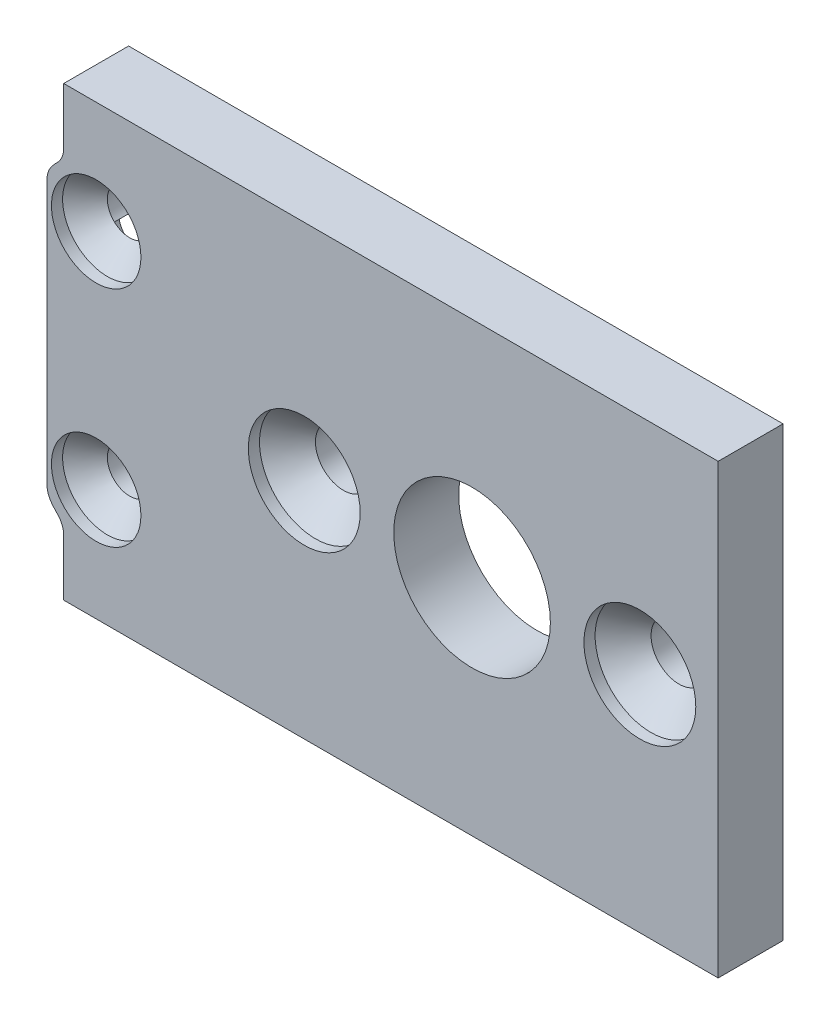
SolidWorks part; units mm, degrees
ref_plane "Front Plane" through (0, 0, 0) normal (0, 0, 1) x (1, 0, 0)
ref_plane "Top Plane" through (0, 0, 0) normal (0, 1, 0) x (1, 0, 0)
ref_plane "Right Plane" through (0, 0, 0) normal (1, 0, 0) x (0, 0, -1)
sketch "Sketch1" plane through (0, 0, 0) normal (0, 0, 1) x (1, 0, 0)
  line L1 (-92.5, 10) -> (92.5, 10)
  line L2 (-92.5, 10) -> (-92.5, -10)
  line L3 (-92.5, -10) -> (92.5, -10)
  line L4 (92.5, 10) -> (92.5, -10)
  line L5 (-92.5, 10) -> (92.5, -10) construction
  line L6 (-92.5, -10) -> (92.5, 10) construction
  point P0 (0, 0)
  dimension "D1" = 20
  dimension "D2" = 185
extrude "Base shape" add sketch "Sketch1" against normal blind 2.9
sketch "Sketch2" plane through (0, 0, 0) normal (0, 0, 1) x (1, 0, 0)
  line L0 (-83.5, 10) -> (-83.5, -10) construction
  line L1 (92.5, 10) -> (-92.5, 10) construction
  line L2 (-92.5, -10) -> (92.5, -10) construction
  line L3 (-92.5, 10) -> (-92.5, -10) construction
  line L4 (-92.5, 0) -> (92.5, 0) construction
  line L5 (92.5, -10) -> (92.5, 10) construction
  line L6 (-73.5, 10) -> (-73.5, -10) construction
  line L7 (0, 10) -> (0, -10) construction
  line L8 (73.5, 5) -> (92.5, 5) construction
  line L9 (-73.5, 3.5) -> (-92.5, 3.5) construction
  line L11 (80.5, -7) -> (66.5, -7)
  line L12 (80.5, -7) -> (80.5, 7)
  line L13 (80.5, 7) -> (66.5, 7)
  line L14 (66.5, -7) -> (66.5, 7)
  line L15 (80.5, -7) -> (66.5, 7) construction
  line L16 (80.5, 7) -> (66.5, -7) construction
  circle A0 centre (-73.5, 0) radius 10
  circle A1 centre (-81, 0) radius 1.25
  circle A2 centre (-66, 0) radius 1.25
  circle A3 centre (-73.5, 0) radius 3.5
  circle A4 centre (73.5, 0) radius 5
  circle A5 centre (66.5, 7) radius 1.25
  circle A6 centre (80.5, 7) radius 1.25
  circle A7 centre (80.5, -7) radius 1.25
  circle A8 centre (66.5, -7) radius 1.25
  dimension "D2" = 20
  dimension "D3" = 2.5
  dimension "D4" = 15
  dimension "D5" = 7
  dimension "D6" = 10
  dimension "D8" = 2.5
  dimension "D1" = 147
  dimension "D7" = 14
extrude "Motor cutouts" cut sketch "Sketch2" against normal up to next contours A5 | A6 | A7 | A8 | A1 | A2 | A3 | A4
hole_wizard "Motor M2.5 countersunks" positions "Sketch3" profile "Sketch4" countersink size "M2.5" standard "ANSI Metric" end condition through all
sketch "Sketch3" plane through (0, 0, 0) normal (0, 0, 1) x (1, 0, 0)
  point P0 (-81, 0)
  point P3 (-66, 0)
  point P7 (66.5, 7)
  point P10 (80.5, 7)
  point P13 (66.5, -7)
  point P16 (80.5, -7)
sketch "Sketch4" plane through (-81, 0, 0) normal (1, 0, 0) x (0, -1, 0)
  line L0 (0, 0) -> (0, 2.9)
  line L1 (0, 2.9) -> (1.25, 2.9)
  line L2 (1.25, 2.9) -> (1.25, 1.75)
  line L3 (1.25, 1.75) -> (2.5, 0.5)
  line L4 (2.5, 0.5) -> (2.5, 0)
  line L6 (2.5, 0) -> (0, 0)
  line L7 (-1.25, 1.75) -> (-2.5, 0.5) construction
  line L11 (0, -6.35) -> (0, 107.95) construction
  dimension "Thru Hole Dia." = 2.5
  dimension "Thru Hole Depth" = 2.9
  dimension "C'Sink Dia." = 5
  dimension "C'Sink Angle" = 90
  dimension "Head Clearance" = 0.5
sketch "Sketch5" plane through (0, 0, -2.9) normal (0, 0, -1) x (-1, 0, 0)
  line L0 (0, 10) -> (0, -10) construction
  line L3 (-92.5, 10) -> (92.5, 10) construction
  line L4 (92.5, -10) -> (-92.5, -10) construction
  line L5 (-60, -7) -> (60, -7) construction
  line L6 (-60, -6) -> (60, -6)
  line L7 (-60, -8) -> (60, -8)
  arc A0 (-60, -6) -> (-60, -8) centre (-60, -7) ccw
  arc A1 (60, -8) -> (60, -6) centre (60, -7) ccw
  point P8 (0, -7)
  dimension "D1" = 120
  dimension "D2" = 2
  dimension "D3" = 2
extrude "PCB slot" cut sketch "Sketch5" against normal blind 0.775
sketch "Sketch6" plane through (0, 0, 0) normal (0, 0, 1) x (1, 0, 0)
  line L0 (90.3, 10) -> (90.3, -10) construction
  line L1 (92.5, 10) -> (-92.5, 10) construction
  line L2 (-92.5, -10) -> (92.5, -10) construction
  line L3 (92.5, -10) -> (92.5, 10) construction
  line L4 (92.5, 0) -> (-92.5, 0) construction
  line L5 (-92.5, 10) -> (-92.5, -10) construction
  line L6 (0, 10) -> (0, -10) construction
  circle A0 centre (90.3, 5) radius 1
  circle A2 centre (90.3, -5) radius 1
  circle A3 centre (-90.3, -5) radius 1
  circle A5 centre (-90.3, 5) radius 1
  dimension "D2" = 2
  dimension "D1" = 2.2
  dimension "D3" = 10
extrude "End plate holes" cut sketch "Sketch6" against normal up to next
hole_wizard "CSK for M2 Flat Head Machine Screw3" positions "Sketch10" profile "Sketch9" countersink size "M2" standard "ANSI Metric" end condition through all
sketch "Sketch10" plane through (0, 0, 0) normal (0, 0, 1) x (1, 0, 0)
  point P2 (90.3, 5)
  point P8 (90.3, -5)
  point P11 (-90.3, 5)
  point P17 (-90.3, -5)
sketch "Sketch9" plane through (90.3, 5, 0) normal (1, 0, 0) x (0, -1, 0)
  line L0 (0, 0) -> (0, 2.9)
  line L1 (0, 2.9) -> (1, 2.9)
  line L2 (1, 2.9) -> (1, 1.5)
  line L3 (1, 1.5) -> (2, 0.5)
  line L4 (2, 0.5) -> (2, 0)
  line L6 (2, 0) -> (0, 0)
  line L7 (-1, 1.5) -> (-2, 0.5) construction
  line L11 (0, -6.35) -> (0, 107.95) construction
  dimension "Thru Hole Dia." = 2
  dimension "Thru Hole Depth" = 2.9
  dimension "C'Sink Dia." = 4
  dimension "C'Sink Angle" = 90
  dimension "Head Clearance" = 0.5
sketch "Sketch12" plane through (0, 0, -2.9) normal (0, 0, -1) x (-1, 0, 0)
  line L0 (-92.5, 0) -> (92.5, 0) construction
  line L1 (-92.5, -10) -> (-92.5, 10) construction
  line L2 (92.5, 10) -> (92.5, -10) construction
  line L3 (-90.3, 5) -> (-90.3, -5) construction
  line L4 (-88.7, 4) -> (-91.9, 0.8) construction
  line L5 (-91.9, 4) -> (-88.7, 4)
  line L6 (-91.9, 4) -> (-91.9, -4)
  line L7 (-91.9, -4) -> (-88.7, -4)
  line L8 (-88.7, 4) -> (-88.7, -4)
  line L9 (-91.9, 4) -> (-88.7, -4) construction
  line L10 (-91.9, -4) -> (-88.7, 4) construction
  line L11 (0, 10) -> (0, -10) construction
  line L12 (-92.5, 10) -> (92.5, 10) construction
  line L13 (92.5, -10) -> (-92.5, -10) construction
  line L14 (91.9, -4) -> (88.7, -4)
  line L15 (91.9, 4) -> (88.7, 4)
  line L16 (91.9, 4) -> (91.9, -4)
  line L17 (88.7, 4) -> (88.7, -4)
  circle A0 centre (-89.4071, 3.2929) radius 1
  circle A1 centre (-91.1929, 3.2929) radius 1
  circle A2 centre (-89.4071, -3.2929) radius 1
  circle A3 centre (-91.1929, -3.2929) radius 1
  circle A4 centre (89.4071, -3.2929) radius 1
  circle A5 centre (91.1929, -3.2929) radius 1
  circle A6 centre (89.4071, 3.2929) radius 1
  circle A7 centre (91.1929, 3.2929) radius 1
  point P10 (-90.3, 0)
  circle M9 centre (-90.3, -5) radius 1
  circle M10 centre (90.3, -5) radius 1
  circle M11 centre (90.3, 5) radius 1
  circle M12 centre (-90.3, 5) radius 1
  dimension "D3" = 2
  dimension "D1" = 3.2
  dimension "D2" = 8
  dimension "D4" = 45
extrude "Tap slots" cut sketch "Sketch12" against normal blind 1.4 contours A7 A6 M11 | A5 A4 M10 | A3 A2 M9 | A1 A0 M12 | A1 L5 M12 | A0 L5 M12 | A3 L7 M9 | A2 L7 M9 | A6 L15 M11 | A7 L15 M11 | A4 L14 M10 | A5 L14 M10 | A1 | A0 | A2 | A3 | L6 L7 L8 L5 | L17 L14 L16 L15 | A6 | A7 | A5 | A4 region at (90.4476, 4.0064, -2.9) region at (90.3, 5.0146, -2.9) region at (90.1524, 4.0064, -2.9) region at (90.4476, -4.0064, -2.9) region at (90.3, -5.0146, -2.9) region at (90.1524, -4.0064, -2.9) region at (-90.4476, -4.0064, -2.9) region at (-90.3, -5.0146, -2.9) region at (-90.1524, -4.0064, -2.9) region at (-90.4476, 4.0064, -2.9) region at (-90.3, 5.0146, -2.9) region at (-90.1524, 4.0064, -2.9)
sketch "Sketch13" plane through (0, 0, 0) normal (0, 0, 1) x (1, 0, 0)
  line L0 (-92.5, -10) -> (92.5, -10) construction
  line L1 (-92.5, 10) -> (-91.75, 10)
  line L2 (-92.5, 10) -> (-92.5, -10)
  line L3 (-92.5, -10) -> (-91.75, -10)
  line L4 (-91.75, 10) -> (-91.75, -10)
  line L5 (-92.5, 0) -> (92.5, 0) construction
  line L6 (92.5, -10) -> (92.5, 10) construction
  line L7 (0, 10) -> (0, -10) construction
  line L8 (92.5, 10) -> (-92.5, 10) construction
  line L9 (92.5, -10) -> (91.75, -10)
  line L10 (91.75, 10) -> (91.75, -10)
  line L11 (92.5, 10) -> (91.75, 10)
  line L12 (92.5, 10) -> (92.5, -10)
  circle A0 centre (-90.3, 5) radius 2.5
  circle A1 centre (-90.3, -5) radius 2.5
  circle A2 centre (90.3, 5) radius 2.5
  circle A3 centre (90.3, -5) radius 2.5
  line M16 (92.5, -10) -> (92.5, 10)
  line M17 (92.5, 10) -> (-92.5, 10)
  line M18 (-92.5, 10) -> (-92.5, -10)
  line M19 (-92.5, -10) -> (92.5, -10)
  dimension "D2" = 5
  dimension "D1" = 0.75
extrude "Cut-Extrude3" cut sketch "Sketch13" against normal up to next contours A0 L4 M17 M18 | A1 L4 M18 M19 | L10 A2 M16 M17 | A3 L10 M16 M19 region at (-92.1406, 8.3301, 0) region at (92.1406, 8.3301, 0) region at (-92.1406, -8.3301, 0) region at (92.1406, -8.3301, 0)
fillet "Fillet1" radius 1 8 edges at (-91.75, -7.0365, -1.45) (-92.5, -6.1874, -1.45) (-92.5, 6.1874, -1.45) (-91.75, 7.0365, -1.45) (92.5, 6.1874, -1.45) (91.75, 7.0365, -1.45) (92.5, -6.1874, -1.45) (91.75, -7.0365, -1.45)
sketch "Sketch14" plane through (0, 0, 0) normal (0, 0, 1) x (1, 0, 0)
  line L0 (-91.75, -10) -> (91.75, -10) construction
  line L1 (-62.5, -10) -> (92.5, -10)
  line L2 (-62.5, -10) -> (-62.5, 10)
  line L3 (-62.5, 10) -> (92.5, 10)
  line L4 (92.5, -10) -> (92.5, 10)
  line L5 (91.75, 10) -> (-91.75, 10) construction
  line L6 (92.5, -5.9) -> (92.5, 5.9) construction
  line L7 (-92.5, 5.9) -> (-92.5, -5.9) construction
  dimension "D1" = 30
extrude "Cut-Extrude4" cut sketch "Sketch14" against normal up to next
